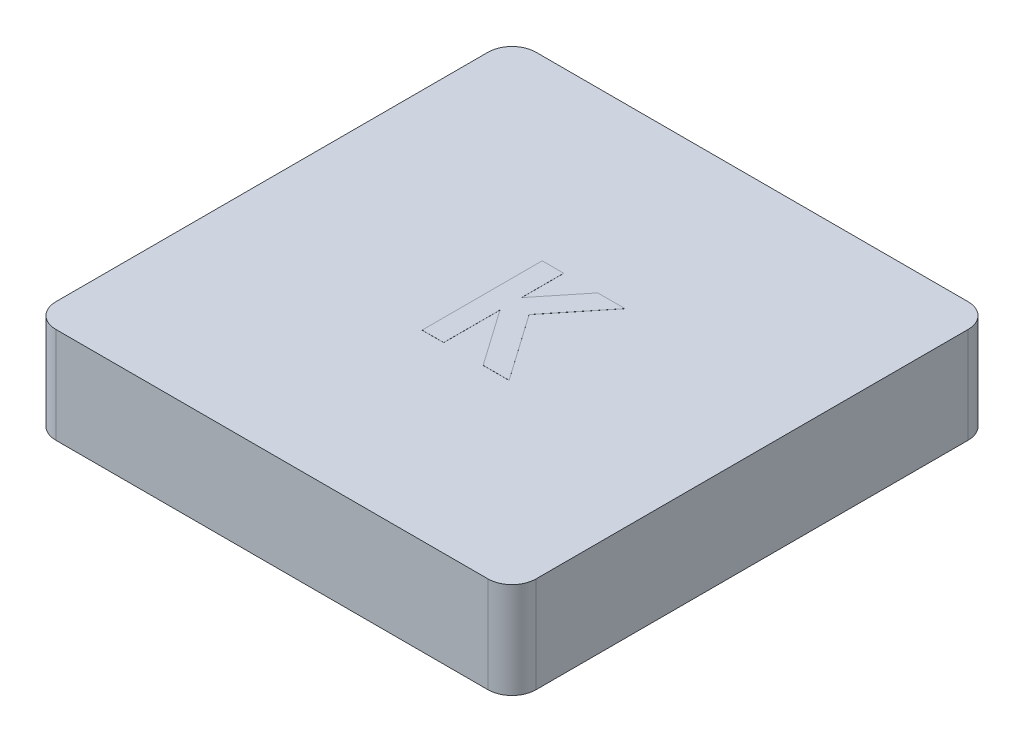
SolidWorks part; units mm, degrees
ref_plane "Front Plane" through (0, 0, 0) normal (0, 0, 1) x (1, 0, 0)
ref_plane "Top Plane" through (0, 0, 0) normal (0, 1, 0) x (1, 0, 0)
ref_plane "Right Plane" through (0, 0, 0) normal (1, 0, 0) x (0, 0, -1)
sketch "Sketch1" plane through (0, 0, 0) normal (0, 1, 0) x (1, 0, 0)
  line L0 (0, 0) -> (12.7, 0)
  line L1 (12.7, 0) -> (12.7, 12.7)
  line L2 (12.7, 12.7) -> (0, 12.7)
  line L3 (0, 12.7) -> (0, 0)
  dimension "D1" = 12.7
  dimension "D2" = 12.7
extrude "Boss-Extrude1" add sketch "Sketch1" along normal blind 2.54
fillet "Fillet1" radius 0.635 4 edges at (0, 1.27, -12.7) (12.7, 1.27, -12.7) (12.7, 1.27, 0) (0, 1.27, 0)
shell "Shell1" thickness 0.635 removed face at (6.35, 0, -6.35)
sketch "Sketch2" plane through (0, 1.905, 0) normal (0, -1, 0) x (-1, 0, 0)
  line L0 (-0.635, 6.35) -> (-12.065, 6.35) construction
  line L1 (-0.635, 12.065) -> (-0.635, 0.635) construction
  line L2 (-12.065, 0.635) -> (-12.065, 12.065) construction
  line L3 (-6.35, 0.635) -> (-6.35, 12.065) construction
  line L4 (-0.635, 0.635) -> (-12.065, 0.635) construction
  line L5 (-12.065, 12.065) -> (-0.635, 12.065) construction
  circle A0 centre (-6.35, 6.35) radius 2.54
  dimension "D1" = 5.08
extrude "Boss-Extrude2" add sketch "Sketch2" along normal up to surface (1.905 mm away) up to face at (6.35, 0, -6.35)
sketch "Sketch3" plane through (0, 2.54, 0) normal (0, 1, 0) x (1, 0, 0)
  line L0 (0, 12.065) -> (0, 0.635) construction
  line L1 (0.635, 0) -> (12.065, 0) construction
  text T0 "<b>K</b>"
  point P1 (0, 0)
  dimension "D1" = 5.1308
  dimension "D2" = 4.826
extrude "Boss-Extrude3" add sketch "Sketch3" along normal blind 0.0025
